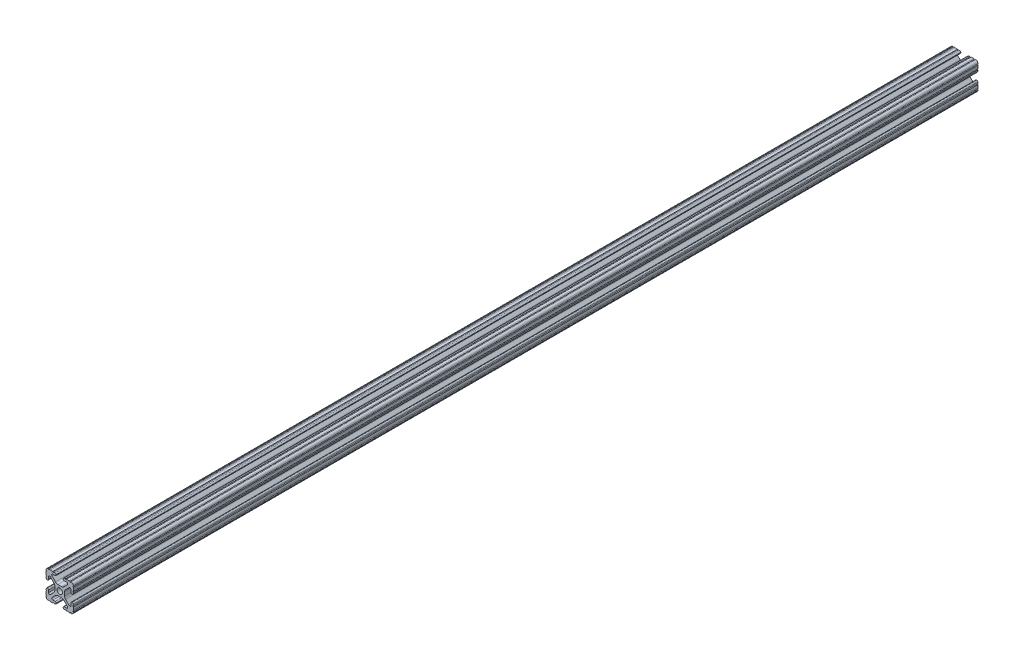
SolidWorks part; units mm, degrees
ref_plane "Front" through (0, 0, 0) normal (0, 0, 1) x (1, 0, 0)
ref_plane "Top" through (0, 0, 0) normal (0, 1, 0) x (1, 0, 0)
ref_plane "Right" through (0, 0, 0) normal (1, 0, 0) x (0, 0, -1)
ref_plane "Bottom" through (0, 25.4, 0) normal (0, 1, 0) x (-1, 0, 0)
ref_plane "Left" through (25.4, 0, 0) normal (1, 0, 0) x (0, 0, -1)
sketch "Sketch1" plane through (0, 0, 0) normal (0, 0, 1) x (1, 0, 0)
  line L0 (25.4334, 2.1492) -> (25.4334, 2.1323)
  line L1 (23.3169, 0.0156) -> (23.3, 0.0156)
  line L2 (22.284, 0.0156) -> (21.2003, 0.0156)
  line L3 (21.2003, 0.0156) -> (19.0664, 0.0901)
  line L4 (6.4007, 0.0901) -> (4.2668, 0.0156)
  line L5 (4.2668, 0.0156) -> (3.1831, 0.0156)
  line L6 (2.1671, 0.0156) -> (2.1502, 0.0156)
  line L7 (0.0335, 2.1323) -> (0.0335, 2.1492)
  line L8 (0.0335, 3.1652) -> (0.0335, 4.249)
  line L9 (0.0335, 4.249) -> (0.1081, 6.3829)
  line L10 (0.108, 19.0484) -> (0.0335, 21.1824)
  line L11 (0.0335, 21.1824) -> (0.0335, 22.2661)
  line L12 (0.0335, 23.2821) -> (0.0335, 23.299)
  line L13 (2.1501, 25.4157) -> (2.1671, 25.4156)
  line L14 (3.1831, 25.4156) -> (4.2668, 25.4156)
  line L15 (4.2668, 25.4156) -> (6.4007, 25.3411)
  line L16 (19.0663, 25.3411) -> (21.2003, 25.4156)
  line L17 (21.2003, 25.4156) -> (22.284, 25.4156)
  line L18 (23.2999, 25.4156) -> (23.3169, 25.4156)
  line L19 (25.4336, 23.299) -> (25.4336, 23.2821)
  line L20 (25.4336, 22.2661) -> (25.4336, 21.1824)
  line L21 (25.4336, 21.1824) -> (25.3591, 19.0485)
  line L22 (25.3589, 6.3829) -> (25.4334, 4.249)
  line L23 (25.4334, 4.249) -> (25.4334, 3.1652)
  line L24 (12.7336, 17.2115) -> (11.1094, 17.2115)
  line L25 (7.6974, 19.3084) -> (8.8644, 18.1414)
  line L26 (8.2292, 12.7156) -> (8.2292, 14.3482)
  line L27 (12.7336, 17.2115) -> (14.3575, 17.2115)
  line L28 (17.2378, 12.7156) -> (17.2378, 14.3484)
  line L29 (17.2378, 12.7156) -> (17.2378, 11.0831)
  line L30 (8.2292, 12.7156) -> (8.2292, 11.0831)
  line L31 (16.6026, 18.1414) -> (19.7969, 21.3357)
  line L32 (18.1678, 8.8381) -> (21.3535, 5.6523)
  line L33 (5.6701, 4.0957) -> (8.8643, 7.2899)
  line L34 (12.7336, 8.2198) -> (11.1094, 8.2198)
  line L35 (12.7336, 8.2198) -> (14.3574, 8.2198)
  line L36 (19.7967, 4.0956) -> (16.6025, 7.2899)
  line L37 (7.2993, 16.5932) -> (4.0415, 19.8511)
  line L38 (7.2993, 8.838) -> (4.0415, 5.5802)
  line L39 (7.6974, 19.3084) -> (5.5981, 21.4076)
  line L40 (7.4161, 25.3057) -> (8.4818, 25.25)
  line L41 (8.4086, 23.0512) -> (6.352, 23.1414)
  line L42 (9.4951, 24.1004) -> (9.4951, 24.2008)
  line L43 (0.1992, 16.9673) -> (0.1435, 18.0331)
  line L44 (1.3488, 15.9541) -> (1.2484, 15.9541)
  line L45 (2.398, 17.0406) -> (2.3077, 19.0972)
  line L46 (0.1435, 7.3983) -> (0.1992, 8.464)
  line L47 (1.2484, 9.4772) -> (1.3488, 9.4773)
  line L48 (2.398, 8.3907) -> (2.3077, 6.3341)
  line L49 (8.4819, 0.1813) -> (7.4161, 0.1256)
  line L50 (9.4951, 1.3309) -> (9.4951, 1.2305)
  line L51 (8.4086, 2.3801) -> (6.352, 2.2898)
  line L52 (18.0509, 0.1256) -> (16.9852, 0.1813)
  line L53 (17.0585, 2.3801) -> (19.1151, 2.2898)
  line L54 (25.2677, 8.464) -> (25.3235, 7.3983)
  line L55 (24.1183, 9.4772) -> (24.2187, 9.4773)
  line L56 (23.0691, 8.3907) -> (23.1594, 6.3341)
  line L57 (25.3235, 18.0331) -> (25.2678, 16.9674)
  line L58 (23.069, 17.0407) -> (23.1593, 19.0973)
  line L59 (16.984, 25.25) -> (18.0509, 25.3057)
  line L60 (15.9709, 24.1004) -> (15.9709, 24.2008)
  line L61 (17.0573, 23.0512) -> (19.1151, 23.1414)
  line L62 (15.972, 1.3309) -> (15.972, 1.2305)
  line L63 (18.1678, 16.5934) -> (21.4254, 19.8511)
  arc A0 (25.4334, 3.1652) -> (25.4334, 2.1492) centre (25.4334, 2.6572) ccw
  arc A1 (23.3169, 0.0156) -> (25.4334, 2.1323) centre (23.3168, 2.1323) ccw
  arc A2 (23.3, 0.0156) -> (22.284, 0.0156) centre (22.792, 0.0105) ccw
  arc A3 (19.0664, 0.0901) -> (18.0509, 0.1256) centre (18.5588, 0.1118) ccw
  arc A4 (7.4161, 0.1256) -> (6.4007, 0.0901) centre (6.9084, 0.1079) ccw
  arc A5 (3.1831, 0.0156) -> (2.1671, 0.0156) centre (2.6751, 0.012) ccw
  arc A6 (0.0335, 2.1323) -> (2.1502, 0.0156) centre (2.1502, 2.1323) ccw
  arc A7 (0.0335, 2.1492) -> (0.0335, 3.1652) centre (0.0335, 2.6572) ccw
  arc A8 (0.1081, 6.3829) -> (0.1435, 7.3983) centre (0.1291, 6.8905) ccw
  arc A9 (0.1435, 18.0331) -> (0.108, 19.0484) centre (0.1258, 18.5408) ccw
  arc A10 (0.0335, 22.2661) -> (0.0335, 23.2821) centre (0.0371, 22.7741) ccw
  arc A11 (2.1501, 25.4157) -> (0.0335, 23.299) centre (2.1502, 23.299) ccw
  arc A12 (2.1671, 25.4156) -> (3.1831, 25.4156) centre (2.6751, 25.412) ccw
  arc A13 (6.4007, 25.3411) -> (7.4161, 25.3057) centre (6.9085, 25.3266) ccw
  arc A14 (18.0509, 25.3057) -> (19.0663, 25.3411) centre (18.5586, 25.3234) ccw
  arc A15 (22.284, 25.4156) -> (23.2999, 25.4156) centre (22.792, 25.412) ccw
  arc A16 (25.4336, 23.299) -> (23.3169, 25.4156) centre (23.3169, 23.299) ccw
  arc A17 (25.4336, 23.2821) -> (25.4336, 22.2661) centre (25.4336, 22.7741) ccw
  arc A18 (25.3591, 19.0485) -> (25.3235, 18.0331) centre (25.3338, 18.5411) ccw
  arc A19 (25.3235, 7.3983) -> (25.3589, 6.3829) centre (25.3412, 6.8906) ccw
  circle A20 centre (12.7336, 12.7156) radius 2.5527
  arc A21 (8.8644, 18.1414) -> (11.1094, 17.2115) centre (11.1094, 20.3865) ccw
  arc A22 (8.2292, 14.3482) -> (7.2993, 16.5932) centre (5.0542, 14.3482) ccw
  arc A23 (14.3575, 17.2115) -> (16.6026, 18.1414) centre (14.3575, 20.3865) ccw
  arc A24 (18.1678, 16.5934) -> (17.2378, 14.3484) centre (20.4128, 14.3484) ccw
  arc A25 (17.2378, 11.0831) -> (18.1678, 8.8381) centre (20.4128, 11.0831) ccw
  arc A26 (7.2993, 8.838) -> (8.2292, 11.0831) centre (5.0542, 11.0831) ccw
  arc A27 (11.1094, 8.2198) -> (8.8643, 7.2899) centre (11.1094, 5.0448) ccw
  arc A28 (16.6025, 7.2899) -> (14.3574, 8.2198) centre (14.3574, 5.0448) ccw
  arc A29 (4.0415, 19.8511) -> (2.3077, 19.0972) centre (3.3231, 19.1327) ccw
  arc A30 (2.3077, 6.3341) -> (4.0415, 5.5802) centre (3.3231, 6.2986) ccw
  arc A31 (5.6701, 4.0957) -> (6.352, 2.2898) centre (6.308, 3.3049) ccw
  arc A32 (19.1151, 2.2898) -> (19.7967, 4.0956) centre (19.1587, 3.3049) ccw
  arc A33 (21.3535, 5.6523) -> (23.1594, 6.3341) centre (22.1443, 6.2902) ccw
  arc A34 (23.1593, 19.0973) -> (21.4254, 19.8511) centre (22.1439, 19.1327) ccw
  arc A35 (19.7969, 21.3357) -> (19.1151, 23.1414) centre (19.1588, 22.1264) ccw
  arc A36 (6.352, 23.1414) -> (5.5981, 21.4076) centre (6.3165, 22.1261) ccw
  arc A37 (9.4951, 24.2008) -> (8.4818, 25.25) centre (8.4452, 24.2008) ccw
  arc A38 (8.4086, 23.0512) -> (9.4951, 24.1004) centre (8.4452, 24.1004) ccw
  arc A39 (0.1992, 16.9673) -> (1.2484, 15.9541) centre (1.2484, 17.004) ccw
  arc A40 (1.3488, 15.9541) -> (2.398, 17.0406) centre (1.3488, 17.004) ccw
  arc A41 (1.2484, 9.4772) -> (0.1992, 8.464) centre (1.2484, 8.4273) ccw
  arc A42 (2.398, 8.3907) -> (1.3488, 9.4773) centre (1.3488, 8.4274) ccw
  arc A43 (8.4819, 0.1813) -> (9.4951, 1.2305) centre (8.4452, 1.2305) ccw
  arc A44 (9.4951, 1.3309) -> (8.4086, 2.3801) centre (8.4452, 1.3309) ccw
  arc A45 (15.972, 1.2305) -> (16.9852, 0.1813) centre (17.0219, 1.2305) ccw
  arc A46 (17.0585, 2.3801) -> (15.972, 1.3309) centre (17.0219, 1.3309) ccw
  arc A47 (25.2677, 8.464) -> (24.2187, 9.4773) centre (24.2185, 8.4274) ccw
  arc A48 (24.1183, 9.4772) -> (23.0691, 8.3907) centre (24.1183, 8.4274) ccw
  arc A49 (24.2186, 15.9542) -> (25.2678, 16.9674) centre (24.2186, 17.004) ccw
  arc A50 (23.069, 17.0407) -> (24.2186, 15.9542) centre (24.118, 16.9992) ccw
  arc A51 (16.984, 25.25) -> (15.9709, 24.2008) centre (17.0207, 24.2008) ccw
  arc A52 (15.9709, 24.1004) -> (17.0573, 23.0512) centre (17.0207, 24.1004) ccw
extrude "Extrude1" add sketch "Sketch1" against normal blind 838.2
ref_axis "Axis1" through (12.7336, 12.7156, 0) along (0, 0, -1)
